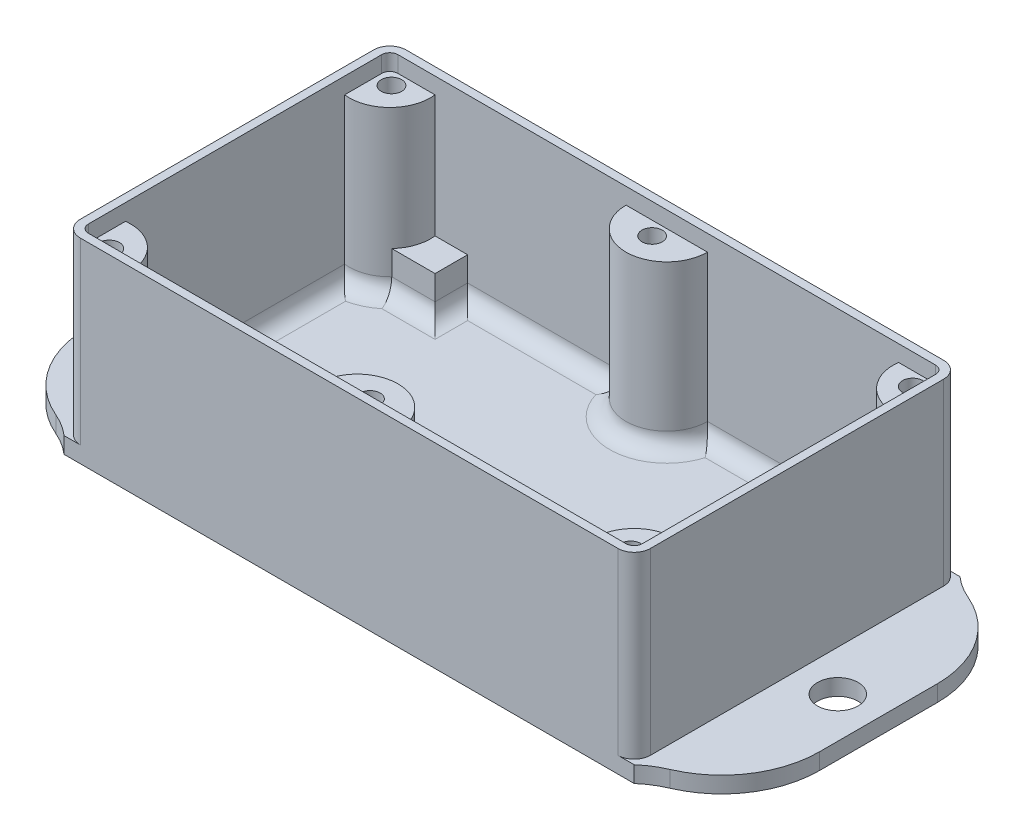
SolidWorks part; units mm, degrees
ref_plane "Front Plane" through (0, 0, 0) normal (0, 0, 1) x (1, 0, 0)
ref_plane "Top Plane" through (0, 0, 0) normal (0, 1, 0) x (1, 0, 0)
ref_plane "Right Plane" through (0, 0, 0) normal (1, 0, 0) x (0, 0, -1)
sketch "Sketch1" plane through (0, 0, 0) normal (0, 1, 0) x (1, 0, 0)
  line L0 (-35, 17.5) -> (-45, 17.5)
  line L1 (-35, -20) -> (35, -20)
  line L2 (-35, -20) -> (-35, 20)
  line L3 (-35, 20) -> (35, 20)
  line L4 (35, -20) -> (35, 20)
  line L5 (-35, -20) -> (35, 20) construction
  line L6 (-35, 20) -> (35, -20) construction
  line L7 (-45, 17.5) -> (-45, -17.5)
  line L8 (-45, -17.5) -> (-35, -17.5)
  line L9 (-57.0188, 0) -> (49.3046, 0) construction
  line L10 (0, 46.4236) -> (0, -38.5478) construction
  line L11 (45, -17.5) -> (35, -17.5)
  line L12 (35, 17.5) -> (45, 17.5)
  line L13 (45, 17.5) -> (45, -17.5)
  point P0 (0, 0)
  point P14 (-53.0925, 0)
  point P15 (47.9204, 0)
  point P16 (-57.6177, 0)
  point P17 (47.3714, 0)
  point P18 (49.3046, 0)
  point P19 (0, 39.3297)
  point P20 (0, 28.8048)
  point P21 (0, -27.6472)
  point P22 (0, 26.8911)
  point P23 (0, 29.3199)
  point P24 (0, 29.3199)
  point P25 (0, 25.7747)
  point P26 (0, 26.2474)
  point P27 (0, 27.9018)
  point P28 (0, 31.2975)
  point P29 (0, 27.3397)
  point P30 (0, 29.1286)
  point P31 (0, 28.9386)
  point P32 (0, 43.9467)
  point P33 (0, 24.9491)
  point P34 (0, 25.5191)
  point P35 (0, 25.3291)
  point P36 (0, 25.3291)
  point P37 (0, 25.899)
  point P38 (0, 39.7672)
  point P39 (0, 24.9491)
  point P40 (0, -28.434)
  point P41 (0, 26.089)
  point P42 (0, 40.1742)
  point P43 (0, -38.5478)
  point P44 (0, 41.4936)
  point P45 (0, 46.4236)
  point P46 (-57.0188, 0)
  dimension "D1" = 70
  dimension "D2" = 40
  dimension "D3" = 10
  dimension "D4" = 35
extrude "Boss-Extrude1" add sketch "Sketch1" along normal blind 2 contours L7 L8 L2 L0 | L13 L12 L4 L11 | L2 L3 L4 L1 region at (-40, 0, 0) region at (40, 0, 0)
fillet "Fillet1" radius 10 4 edges at (35, 1, -17.5) (-35, 1, -17.5) (-35, 1, 17.5) (35, 1, 17.5)
sketch "Sketch2" plane through (0, 2, 0) normal (0, 1, 0) x (1, 0, 0)
  line L0 (-32, 19) -> (32, 19)
  line L1 (-33, 20) -> (33, 20)
  line L2 (-35, 18) -> (-35, -18)
  line L3 (-33, -20) -> (33, -20)
  line L4 (35, 18) -> (35, -18)
  line L5 (34, 17) -> (34, -17)
  line L6 (-32, -19) -> (32, -19)
  line L7 (-34, 17) -> (-34, -17)
  line L8 (-34, -19) -> (34, -19) construction
  line L9 (-34, 19) -> (-34, -19) construction
  line L10 (-35, 20) -> (-35, -20) construction
  line L11 (-35, -20) -> (35, -20) construction
  line L12 (34, 19) -> (34, -19) construction
  line L13 (35, 20) -> (35, -20) construction
  line L14 (-34, 19) -> (34, 19) construction
  line L15 (-35, 20) -> (35, 20) construction
  arc A0 (-32, -19) -> (-34, -17) centre (-32, -17) cw
  arc A1 (-35, -18) -> (-33, -20) centre (-33, -18) ccw
  arc A2 (34, -17) -> (32, -19) centre (32, -17) cw
  arc A3 (33, -20) -> (35, -18) centre (33, -18) ccw
  arc A4 (32, 19) -> (34, 17) centre (32, 17) cw
  arc A5 (33, 20) -> (35, 18) centre (33, 18) cw
  arc A6 (-32, 19) -> (-34, 17) centre (-32, 17) ccw
  arc A7 (-33, 20) -> (-35, 18) centre (-33, 18) ccw
  dimension "D2" = 2
  dimension "D3" = 35
  dimension "D4" = 35
  dimension "D5" = 20
  dimension "D6" = 20
  dimension "D1" = 1
extrude "Boss-Extrude2" add sketch "Sketch2" along normal blind 20
sketch "Sketch3" plane through (0, 2, 0) normal (0, 1, 0) x (1, 0, 0)
  line L0 (32, 19) -> (-32, 19) construction
  line L1 (-32, -19) -> (32, -19) construction
  line L2 (-28.4486, 19) -> (-32, 19)
  line L3 (-5, -19) -> (5, -19)
  line L4 (28.4486, -19) -> (32, -19)
  line L5 (5, 19) -> (-5, 19)
  line L6 (-32, -19) -> (32, -19)
  line L7 (-34, 17) -> (-34, -17)
  line L8 (32, 19) -> (-32, 19)
  line L9 (34, -17) -> (34, 17)
  line L10 (-32, -19) -> (-28.4486, -19)
  line L11 (-34, 17) -> (-34, 13.4486)
  line L12 (32, 19) -> (28.4486, 19)
  line L13 (34, -17) -> (34, -13.4486)
  line L14 (-34, -13.4486) -> (-34, -17)
  line L15 (34, 13.4486) -> (34, 17)
  arc A0 (-34, 13.4486) -> (-28.4486, 19) centre (-33.4142, 18.4142) ccw
  arc A1 (-32, 19) -> (-34, 17) centre (-32, 17) ccw construction
  arc A2 (28.4486, 19) -> (34, 13.4486) centre (33.4142, 18.4142) ccw
  arc A3 (34, 17) -> (32, 19) centre (32, 17) ccw construction
  arc A4 (34, -13.4486) -> (28.4486, -19) centre (33.4142, -18.4142) ccw
  arc A5 (32, -19) -> (34, -17) centre (32, -17) ccw construction
  arc A6 (-28.4486, -19) -> (-34, -13.4486) centre (-33.4142, -18.4142) ccw
  arc A7 (-34, -17) -> (-32, -19) centre (-32, -17) ccw construction
  arc A8 (-5, 19) -> (5, 19) centre (0, 19) ccw
  arc A9 (5, -19) -> (-5, -19) centre (0, -19) ccw
  arc A14 (-34, -17) -> (-32, -19) centre (-32, -17) ccw
  arc A15 (-32, 19) -> (-34, 17) centre (-32, 17) ccw
  arc A16 (34, 17) -> (32, 19) centre (32, 17) ccw
  arc A17 (32, -19) -> (34, -17) centre (32, -17) ccw
  arc A18 (-34, -17) -> (-32, -19) centre (-32, -17) ccw
  arc A19 (-32, 19) -> (-34, 17) centre (-32, 17) ccw
  arc A20 (34, 17) -> (32, 19) centre (32, 17) ccw
  arc A21 (32, -19) -> (34, -17) centre (32, -17) ccw
  dimension "D1" = 10
  dimension "D2" = 0
extrude "Boss-Extrude3" add sketch "Sketch3" along normal blind 20
sketch "Sketch4" plane through (0, 22, 0) normal (0, 1, 0) x (1, 0, 0)
  line L0 (-33, -19) -> (33, -19)
  line L1 (34, -18) -> (34, 18)
  line L2 (33, 19) -> (-33, 19)
  line L3 (-34, 18) -> (-34, -18)
  line L4 (-33, -20) -> (33, -20)
  line L5 (35, -18) -> (35, 18)
  line L6 (33, 20) -> (-33, 20)
  line L7 (-35, 18) -> (-35, -18)
  line L8 (-33, -20) -> (33, -20)
  line L9 (35, -18) -> (35, 18)
  line L10 (33, 20) -> (-33, 20)
  line L11 (-35, 18) -> (-35, -18)
  arc A0 (33, -19) -> (34, -18) centre (33, -18) ccw
  arc A1 (34, 18) -> (33, 19) centre (33, 18) ccw
  arc A2 (-33, 19) -> (-34, 18) centre (-33, 18) ccw
  arc A3 (-34, -18) -> (-33, -19) centre (-33, -18) ccw
  arc A4 (-35, -18) -> (-33, -20) centre (-33, -18) ccw
  arc A5 (33, -20) -> (35, -18) centre (33, -18) ccw
  arc A6 (35, 18) -> (33, 20) centre (33, 18) ccw
  arc A7 (-33, 20) -> (-35, 18) centre (-33, 18) ccw
  arc A8 (-35, -18) -> (-33, -20) centre (-33, -18) ccw
  arc A9 (33, -20) -> (35, -18) centre (33, -18) ccw
  arc A10 (35, 18) -> (33, 20) centre (33, 18) ccw
  arc A11 (-33, 20) -> (-35, 18) centre (-33, 18) ccw
  dimension "D1" = 0
  dimension "D2" = 1
extrude "Boss-Extrude4" add sketch "Sketch4" along normal blind 2
hole_wizard "Tap Drill for M3 Tap1" positions "3DSketch1" profile "Sketch6" hole size "M3" standard "ISO"
sketch3d "3DSketch1"
  line L1 (50.2815, 0, 0) -> (-61.0487, 0, 0) construction
  point P0 (-32.1186, 22, -17.3205)
  point P2 (-0.1186, 22, -17.3205)
  point P4 (31.8814, 22, -17.3205)
  point P6 (31.8814, 22, 17.3205)
  point P8 (-0.1186, 22, 17.3201)
  point P10 (-32.1186, 22, 17.3205)
  point P21 (0, 0, 0)
  point P22 (0, 0, 0)
  point P23 (-32.1186, 22, -17.3205)
  point P24 (0, 0, 0)
  point P25 (0, 0, 0)
  point P26 (0, 0, 0)
  dimension "D1" = 32
  dimension "D2" = 32
  dimension "D3" = 28
  dimension "D4" = 28
  dimension "D5" = 28
  dimension "D6" = 32
  dimension "D7" = 28
  dimension "D8" = 32
sketch "Sketch6" plane through (-32.1186, 22, -17.3205) normal (1, 0, 0) x (0, 0, 1)
  line L0 (0, 0) -> (0, 8.2511)
  line L1 (0, 8.2511) -> (1.25, 7.5)
  line L2 (1.25, 7.5) -> (1.25, 0)
  line L5 (1.25, 0) -> (0, 0)
  line L10 (0, 8.2511) -> (-1.25, 7.5) construction
  line L11 (0, -6.35) -> (0, 107.95) construction
  dimension "Hole Dia." = 2.5
  dimension "Hole Depth" = 7.5
  dimension "Drill Angle" = 118
sketch "Sketch7" plane through (0, 2, 0) normal (0, 1, 0) x (1, 0, 0)
  line L1 (-28.4486, 19) -> (-24.4486, 19)
  line L2 (-28.4486, 19) -> (-28.4486, 17.8284)
  line L3 (-29.7614, 15) -> (-24.4486, 15)
  line L4 (-24.4486, 19) -> (-24.4486, 15)
  line L5 (-28.4486, -19) -> (-24.4486, -19)
  line L6 (-28.4486, -19) -> (-28.4486, -17.8284)
  line L7 (-29.7614, -15) -> (-24.4486, -15)
  line L8 (-24.4486, -19) -> (-24.4486, -15)
  arc A0 (-34, 13.4486) -> (-28.4486, 19) centre (-33.4142, 18.4142) ccw construction
  arc A1 (-29.7614, 15) -> (-28.4486, 17.8284) centre (-33.4142, 18.4142) ccw
  arc A2 (-28.4486, -19) -> (-34, -13.4486) centre (-33.4142, -18.4142) ccw construction
  arc A3 (-28.4486, -17.8284) -> (-29.7614, -15) centre (-33.4142, -18.4142) ccw
  dimension "D1" = 4
  dimension "D2" = 4
  dimension "D4" = 4
extrude "Boss-Extrude5" add sketch "Sketch7" along normal blind 5
fillet "Fillet2" [suppressed] radius 2
mirror "Mirror1" about plane through (0, 0, 0) normal (1, 0, 0) of "Boss-Extrude5", "Fillet2"
fillet "Fillet4" radius 2 20 edges at (-31.6957, 2, 13.7188) (-14.7243, 2, 19) (0, 2, 14) (14.7243, 2, 19) (31.6957, 2, 13.7188) (34, 2, 0) (31.6957, 2, -13.7188) (14.7243, 2, -19) (0, 2, -14) (-31.6957, 2, -13.7188) (-34, 2, 0) (-14.7243, 2, -19) (24.4486, 2, 17) (-24.4486, 2, 17) (-27.105, 2, 15) (-27.105, 2, -15) (-24.4486, 2, -17) (24.4486, 2, -17) (27.105, 2, -15) (27.105, 2, 15)
fillet "Fillet5" radius 12 4 edges at (45, 1, -17.5) (45, 1, 17.5) (-45, 1, -17.5) (-45, 1, 17.5)
sketch "Sketch9" plane through (0, 2, 0) normal (0, 1, 0) x (1, 0, 0)
  line L0 (-53.6179, 0) -> (62.8265, 0) construction
  circle A0 centre (-40, 0) radius 2.5
  dimension "D1" = 5
  dimension "D2" = 40
extrude "Cut-Extrude1" cut sketch "Sketch9" against normal up to next
mirror "Mirror2" about plane through (0, 0, 0) normal (1, 0, 0) of "Cut-Extrude1"
